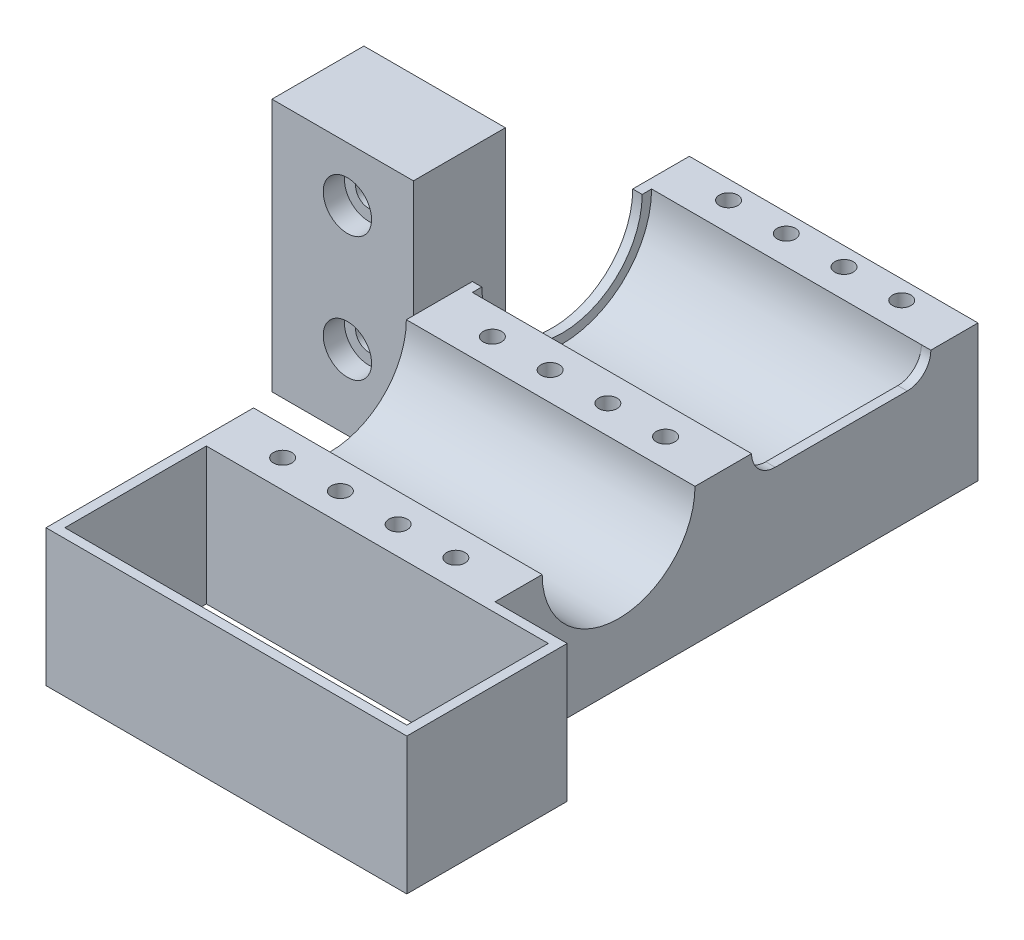
SolidWorks part; units mm, degrees
ref_plane "Front Plane" through (0, 0, 0) normal (0, 0, 1) x (1, 0, 0)
ref_plane "Top Plane" through (0, 0, 0) normal (0, 1, 0) x (1, 0, 0)
ref_plane "Right Plane" through (0, 0, 0) normal (1, 0, 0) x (0, 0, -1)
sketch "Sketch1" plane through (0, 0, 0) normal (1, 0, 0) x (0, 0, -1)
  line L0 (51.2, 42.0261) -> (51.2, 0) construction
  line L1 (0, 0) -> (102.4, 0)
  line L2 (0, 0) -> (0, 29)
  line L3 (102.4, 0) -> (102.4, 29)
  line L4 (0, 29) -> (10, 29) construction
  line L6 (42.4, 29) -> (54.4, 29) construction
  line L7 (42.4, 29) -> (54.4, 29)
  line L8 (0, 29) -> (10, 29)
  line L10 (42.4, 29) -> (54.4, 29)
  line L11 (92.4, 29) -> (102.4, 29)
  arc A0 (10, 29) -> (42.4, 29) centre (26.2, 29) ccw
  arc A1 (54.4, 29) -> (92.4, 29) centre (73.4, 29) ccw
  point P15 (73.4, 10)
  dimension "D3" = 19
  dimension "D4" = 16.2
  dimension "D1" = 10
  dimension "D2" = 12
  dimension "D5" = 10
extrude "Boss-Extrude1" add sketch "Sketch1" along normal blind 61.2 contours L8 L2 L1 L3 L7 region at (0, 11.0871, -50.0531)
sketch "Sketch7" plane through (0, 0, 0) normal (-1, 0, 0) x (0, 0, 1)
  line L0 (0, 0) -> (-102.4, 0) construction
  line L1 (-63.4, 0) -> (-43.8992, 0)
  line L2 (-63.4, 0) -> (-63.4, 53.7409)
  line L3 (-63.4, 53.7409) -> (-43.8992, 53.7409)
  line L4 (-43.8992, 0) -> (-43.8992, 53.7409)
  line L5 (-42.4, 29) -> (-54.4, 29) construction
  line L6 (-42.4, 29) -> (-54.4, 29) construction
  arc A0 (-92.4, 29) -> (-54.4, 29) centre (-73.4, 29) ccw construction
  arc A1 (-92.4, 29) -> (-54.4, 29) centre (-73.4, 29) ccw construction
  circle A2 centre (-73.4, 29) radius 6 construction
  dimension "D1" = 12
  dimension "D2" = 10
  dimension "D3" = 1.4992
extrude "Boss-Extrude2" add sketch "Sketch7" along normal blind 30
sketch "Sketch14" plane through (61.2, 0, 0) normal (1, 0, 0) x (0, 0, -1)
  line L0 (54.4, 29) -> (92.4, 29)
  arc A0 (54.4, 29) -> (92.4, 29) centre (73.4, 29) ccw construction
  arc A1 (54.4, 29) -> (92.4, 29) centre (73.4, 29) ccw
extrude "Boss-Extrude3" add sketch "Sketch14" against normal blind 2
sketch "Sketch19" plane through (0, 0, 0) normal (-1, 0, 0) x (0, 0, 1)
  line L1 (-90.4, 29) -> (-92.4, 29)
  line L2 (-56.4, 29) -> (-54.4, 29)
  arc A5 (-63.4, 12.8445) -> (-54.4, 29) centre (-73.4, 29) ccw construction
  arc A7 (-92.4, 29) -> (-63.4, 12.8445) centre (-73.4, 29) ccw construction
  arc A8 (-63.4, 12.8445) -> (-54.4, 29) centre (-73.4, 29) ccw
  arc A9 (-92.4, 29) -> (-63.4, 12.8445) centre (-73.4, 29) ccw
  arc A10 (-90.4, 29) -> (-64.4526, 14.5451) centre (-73.4, 29) ccw
  arc A11 (-64.4526, 14.5451) -> (-56.4, 29) centre (-73.4, 29) ccw
  dimension "D1" = 2
extrude "Boss-Extrude4" add sketch "Sketch19" against normal blind 2
sketch "Sketch26" plane through (0, 0, 0) normal (0, 1, 0) x (1, 0, 0)
  line L0 (2, -2) -> (74.5, -2)
  line L1 (0, 0) -> (76.5, 0)
  line L2 (0, 0) -> (0, -34)
  line L3 (0, -34) -> (76.5, -34)
  line L4 (76.5, 0) -> (76.5, -34)
  line L5 (74.5, -2) -> (74.5, -32)
  line L6 (2, -32) -> (74.5, -32)
  line L7 (2, -2) -> (2, -32)
  dimension "D1" = 34
  dimension "D2" = 76.5
  dimension "D3" = 2
extrude "Boss-Extrude5" add sketch "Sketch26" along normal blind 29
sketch "Sketch8" plane through (0, 0, -63.4) normal (0, 0, -1) x (-1, 0, 0)
  line L0 (30, 53.7409) -> (0, 53.7409) construction
  line L1 (0, 53.7409) -> (0, 15.2523) construction
  line L2 (30, 53.7409) -> (0, 53.7409) construction
  line L3 (0, 53.7409) -> (0, 15.2523) construction
  line L5 (-2, 29) -> (0, 29) construction
  line L12 (3.5, 29) -> (45.8321, 29) construction
  line L14 (-2, 29) -> (-2, 10) construction
  line L15 (-2, 29) -> (-2, 10) construction
  line L16 (-2, 29) -> (0, 29) construction
  circle A0 centre (14, 42.2) radius 2.75
  circle A1 centre (14, 15.8) radius 2.75
  dimension "D3" = 5.5
  dimension "D2" = 14
  dimension "D1" = 13.2
  dimension "D4" = 13.2
extrude "Cut-Extrude1" cut sketch "Sketch8" against normal up to surface (19.5008 mm away) up to face at (-12, 27.2964, -43.8992)
sketch "Sketch9" plane through (0, 0, -63.4) normal (0, 0, -1) x (-1, 0, 0)
  circle A0 centre (14, 42.2) radius 5.125
  circle A1 centre (14, 15.8) radius 5.125
  dimension "D1" = 10.25
extrude "Cut-Extrude2" cut sketch "Sketch9" against normal blind 4.5
sketch "Sketch10" plane through (0, 0, -43.8992) normal (0, 0, 1) x (1, 0, 0)
  circle A0 centre (-14, 42.2) radius 5.125
  circle A1 centre (-14, 15.8) radius 5.125
  dimension "D1" = 10.25
extrude "Cut-Extrude8" cut sketch "Sketch10" against normal blind 4.5
sketch "Sketch22" plane through (0, 29, 0) normal (0, 1, 0) x (1, 0, 0)
  line L0 (61.2, 42.4) -> (0, 42.4) construction
  line L1 (59.2, 54.4) -> (2, 54.4) construction
  line L2 (61.2, 42.4) -> (0, 42.4) construction
  line L3 (59.2, 54.4) -> (2, 54.4) construction
  line L4 (30.6, 54.4) -> (30.6, 42.4) construction
  line L5 (30.6, 48.4) -> (0, 48.4) construction
  line L6 (30.6, 48.4) -> (61.2, 48.4) construction
  line L7 (61.2, 42.4) -> (61.2, 102.4) construction
  line L8 (61.2, 10) -> (61.2, 42.4) construction
  line L9 (59.2, 92.4) -> (59.2, 54.4) construction
  line L10 (61.2, 10) -> (61.2, 42.4) construction
  line L11 (59.2, 92.4) -> (59.2, 54.4) construction
  line L12 (59.2, 73.4) -> (-4.6102, 73.4) construction
  line L13 (61.2, 26.2) -> (-9.4707, 26.2) construction
  line L14 (-21.9217, 98.47) -> (51.6485, 98.47) construction
  line L15 (76.5, 0) -> (61.2, 0) construction
  line L16 (10.6744, 3.93) -> (59.5979, 3.93) construction
  line L17 (0, 43.8992) -> (0, 63.4) construction
  line L18 (61.2, 102.4) -> (0, 102.4) construction
  line L19 (0, 43.8992) -> (0, 63.4) construction
  circle A0 centre (12.24, 48.4) radius 1.95
  circle A1 centre (24.48, 48.4) radius 1.95
  circle A2 centre (36.72, 48.4) radius 1.95
  circle A3 centre (48.96, 48.4) radius 1.95
  circle A5 centre (48.96, 98.47) radius 1.95
  circle A8 centre (24.48, 98.47) radius 1.95
  circle A9 centre (12.24, 98.47) radius 1.95
  circle A10 centre (36.72, 3.93) radius 1.95
  circle A11 centre (48.96, 3.93) radius 1.95
  circle A14 centre (12.24, 3.93) radius 1.95
  circle A15 centre (36.72, 98.47) radius 1.95
  circle A16 centre (24.48, 3.93) radius 1.95
  dimension "D1" = 3.9
  dimension "D7" = 3.93
  dimension "D8" = 3.93
  dimension "D2" = 12.24
  dimension "D3" = 61.2
  dimension "D4" = 12.24
  dimension "D5" = 12.24
  dimension "D6" = 12.24
extrude "Cut-Extrude9" cut sketch "Sketch22" against normal up to surface (29 mm away) up to face at (21.54, 0, -35.1398)
sketch "Sketch24" plane through (0, 0, 0) normal (0, -1, 0) x (1, 0, 0)
  line L0 (74.5, 2) -> (2, 2) construction
  line L1 (15.7041, -3.93) -> (13.9721, -0.93)
  line L2 (13.9721, -0.93) -> (10.5079, -0.93)
  line L3 (10.5079, -0.93) -> (8.7759, -3.93)
  line L4 (8.7759, -3.93) -> (10.5079, -6.93)
  line L5 (10.5079, -6.93) -> (13.9721, -6.93)
  line L6 (13.9721, -6.93) -> (15.7041, -3.93)
  line L7 (27.9441, -3.93) -> (26.2121, -0.93)
  line L8 (26.2121, -0.93) -> (22.7479, -0.93)
  line L9 (22.7479, -0.93) -> (21.0159, -3.93)
  line L10 (21.0159, -3.93) -> (22.7479, -6.93)
  line L11 (22.7479, -6.93) -> (26.2121, -6.93)
  line L12 (26.2121, -6.93) -> (27.9441, -3.93)
  line L13 (40.1841, -3.93) -> (38.4521, -0.93)
  line L14 (38.4521, -0.93) -> (34.9879, -0.93)
  line L15 (34.9879, -0.93) -> (33.2559, -3.93)
  line L16 (33.2559, -3.93) -> (34.9879, -6.93)
  line L17 (34.9879, -6.93) -> (38.4521, -6.93)
  line L18 (38.4521, -6.93) -> (40.1841, -3.93)
  line L19 (52.4241, -3.93) -> (50.6921, -0.93)
  line L20 (50.6921, -0.93) -> (47.2279, -0.93)
  line L21 (47.2279, -0.93) -> (45.4959, -3.93)
  line L22 (45.4959, -3.93) -> (47.2279, -6.93)
  line L23 (47.2279, -6.93) -> (50.6921, -6.93)
  line L24 (50.6921, -6.93) -> (52.4241, -3.93)
  line L25 (45.4959, -48.4009) -> (47.2287, -51.4005)
  line L26 (47.2287, -51.4005) -> (50.6928, -51.3995)
  line L27 (50.6928, -51.3995) -> (52.4241, -48.3991)
  line L28 (52.4241, -48.3991) -> (50.6913, -45.3995)
  line L29 (50.6913, -45.3995) -> (47.2272, -45.4005)
  line L30 (47.2272, -45.4005) -> (45.4959, -48.4009)
  line L31 (33.2559, -48.4007) -> (34.9885, -51.4003)
  line L32 (34.9885, -51.4003) -> (38.4526, -51.3997)
  line L33 (38.4526, -51.3997) -> (40.1841, -48.3993)
  line L34 (40.1841, -48.3993) -> (38.4515, -45.3997)
  line L35 (38.4515, -45.3997) -> (34.9874, -45.4003)
  line L36 (34.9874, -45.4003) -> (33.2559, -48.4007)
  line L37 (21.0159, -48.4005) -> (22.7484, -51.4003)
  line L38 (22.7484, -51.4003) -> (26.2125, -51.3997)
  line L39 (26.2125, -51.3997) -> (27.9441, -48.3995)
  line L40 (27.9441, -48.3995) -> (26.2116, -45.3997)
  line L41 (26.2116, -45.3997) -> (22.7475, -45.4003)
  line L42 (22.7475, -45.4003) -> (21.0159, -48.4005)
  line L43 (8.7759, -48.4005) -> (10.5083, -51.4002)
  line L44 (10.5083, -51.4002) -> (13.9724, -51.3998)
  line L45 (13.9724, -51.3998) -> (15.7041, -48.3995)
  line L46 (15.7041, -48.3995) -> (13.9717, -45.3998)
  line L47 (13.9717, -45.3998) -> (10.5076, -45.4002)
  line L48 (10.5076, -45.4002) -> (8.7759, -48.4005)
  line L49 (10.5079, -95.47) -> (8.7759, -98.47)
  line L50 (8.7759, -98.47) -> (10.5079, -101.47)
  line L51 (10.5079, -101.47) -> (13.9721, -101.47)
  line L52 (13.9721, -101.47) -> (15.7041, -98.47)
  line L53 (15.7041, -98.47) -> (13.9721, -95.47)
  line L54 (13.9721, -95.47) -> (10.5079, -95.47)
  line L55 (22.7479, -95.47) -> (21.0159, -98.47)
  line L56 (21.0159, -98.47) -> (22.7479, -101.47)
  line L57 (22.7479, -101.47) -> (26.2121, -101.47)
  line L58 (26.2121, -101.47) -> (27.9441, -98.47)
  line L59 (27.9441, -98.47) -> (26.2121, -95.47)
  line L60 (26.2121, -95.47) -> (22.7479, -95.47)
  line L61 (34.9879, -95.47) -> (33.2559, -98.47)
  line L62 (33.2559, -98.47) -> (34.9879, -101.47)
  line L63 (34.9879, -101.47) -> (38.4521, -101.47)
  line L64 (38.4521, -101.47) -> (40.1841, -98.47)
  line L65 (40.1841, -98.47) -> (38.4521, -95.47)
  line L66 (38.4521, -95.47) -> (34.9879, -95.47)
  line L67 (47.2279, -95.47) -> (45.4959, -98.47)
  line L68 (45.4959, -98.47) -> (47.2279, -101.47)
  line L69 (47.2279, -101.47) -> (50.6921, -101.47)
  line L70 (50.6921, -101.47) -> (52.4241, -98.47)
  line L71 (52.4241, -98.47) -> (50.6921, -95.47)
  line L72 (50.6921, -95.47) -> (47.2279, -95.47)
  line L73 (61.2, -102.4) -> (0, -102.4) construction
  circle A0 centre (12.24, -3.93) radius 3 construction
  circle A1 centre (24.48, -3.93) radius 3 construction
  circle A2 centre (36.72, -3.93) radius 3 construction
  circle A3 centre (48.96, -3.93) radius 3 construction
  circle A4 centre (48.96, -48.4) radius 3 construction
  circle A5 centre (36.72, -48.4) radius 3 construction
  circle A6 centre (24.48, -48.4) radius 3 construction
  circle A7 centre (12.24, -48.4) radius 3 construction
  circle A8 centre (12.24, -98.47) radius 3 construction
  circle A9 centre (24.48, -98.47) radius 3 construction
  circle A10 centre (36.72, -98.47) radius 3 construction
  circle A11 centre (48.96, -98.47) radius 3 construction
  dimension "D1" = 6
extrude "Cut-Extrude10" cut sketch "Sketch24" against normal blind 4.5
sketch "Sketch25" plane through (61.2, 0, 0) normal (1, 0, 0) x (0, 0, -1)
  line L0 (59.4, 29) -> (87.4, 29) construction
  line L1 (42.4, 29) -> (102.4, 29) construction
  line L2 (59.4, 34) -> (87.4, 34)
  line L3 (59.4, 24) -> (87.4, 24)
  line L6 (92.4, 29) -> (54.4, 29) construction
  line L7 (92.4, 29) -> (54.4, 29) construction
  arc A0 (59.4, 34) -> (59.4, 24) centre (59.4, 29) ccw
  arc A1 (87.4, 24) -> (87.4, 34) centre (87.4, 29) ccw
  point P5 (73.4, 29)
  point P12 (92.4, 29)
  dimension "D1" = 10
extrude "Cut-Extrue11" cut sketch "Sketch25" against normal blind 2
chamfer "Chamfer1" [suppressed] distance 1 angle 45
split "Split1" bodies to split 126 resulting bodies 128 129 split by face at (0, 35.9789, -53.8698)
equation "\"MotorDIA\"= 37' Motor Diameter"
equation "\"SyringeDIA\"= 31.4'60ml Syringe Diameter"
equation "\"MotorShaftDIA\"= 6'Motor Shaft Dia"
equation "\"MotorKeyway\"= 1'Motor Shaft Keyway Depth"
equation "\"MotorLength\"= 56.7'Motor Length Excluding Shaft"
equation "\"SyringeLength\"= 117.3'60ml Syringe Length Excluding Nozzle"
equation "\"3Dtol\"= .5'Sizing Tolerance for 3D printed parts"
equation "\"ChamberDIA\"= 100 - 4'Buoyancy Chamber inner Diameter"
equation "\"ChamberThk\"= 2mm'Buoyancy Chamber Wall Thickness"
equation "\"D4@Sketch1\"=\"SyringeDIA\"/2+\"3Dtol\""
equation "\"D3@Sketch1\"=\"MotorDIA\"/2+\"3Dtol\""
equation "\"D1@Boss-Extrude1\"=\"MotorLength\"+\"3Dtol\"+4"
equation "\"D4@Sketch8\"=\"D1@Sketch8\""
equation "\"BearingOD\"= 10"
equation "\"BearingID\"= 4"
equation "\"Bearingwidth\"= 4"
equation "\"ShaftDIA\"= 4"
equation "\"D2@Sketch22\"=\"D3@Sketch22\"/5"
equation "\"D4@Sketch22\"=\"D2@Sketch22\""
equation "\"D5@Sketch22\"=\"D4@Sketch22\""
equation "\"D6@Sketch22\"=\"D5@Sketch22\""
